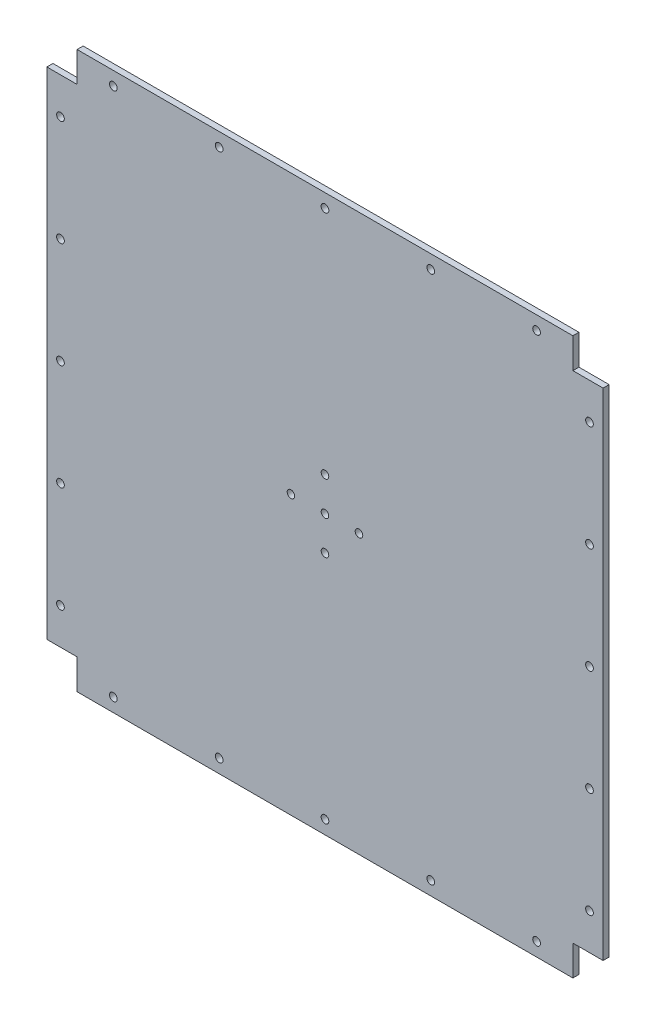
SolidWorks part; units mm, degrees
ref_plane "前视基准面" through (0, 0, 0) normal (0, 0, 1) x (1, 0, 0)
ref_plane "上视基准面" through (0, 0, 0) normal (0, 1, 0) x (1, 0, 0)
ref_plane "右视基准面" through (0, 0, 0) normal (1, 0, 0) x (0, 0, -1)
sketch "草图1" plane through (0, 0, 0) normal (0, 0, 1) x (1, 0, 0)
  line L1 (184, -184) -> (-184, -184)
  line L2 (184, -184) -> (184, 184)
  line L3 (184, 184) -> (-184, 184)
  line L4 (-184, -184) -> (-184, 184)
  line L5 (184, -184) -> (-184, 184) construction
  line L6 (184, 184) -> (-184, -184) construction
  point P0 (0, 0)
  dimension "D1" = 368
  dimension "D2" = 368
extrude "凸台-拉伸1" add sketch "草图1" along normal blind 4
sketch "草图3" plane through (0, 0, 4) normal (0, 0, 1) x (1, 0, 0)
  line L0 (0, -184) -> (0, -175) construction
  line L1 (-184, -184) -> (184, -184) construction
  circle A0 centre (0, -175) radius 2.55
  circle A1 centre (70, -175) radius 2.55
  circle A2 centre (140, -175) radius 2.55
  circle A3 centre (-70, -175) radius 2.55
  circle A4 centre (-140, -175) radius 2.55
  circle A30 centre (-175, 140) radius 2.55
  circle A31 centre (-175, 70) radius 2.55
  circle A32 centre (-175, -70) radius 2.55
  circle A33 centre (-175, -140) radius 2.55
  circle A34 centre (-175, 0) radius 2.55
  circle A35 centre (140, 175) radius 2.55
  circle A36 centre (70, 175) radius 2.55
  circle A37 centre (-70, 175) radius 2.55
  circle A38 centre (-140, 175) radius 2.55
  circle A39 centre (0, 175) radius 2.55
  circle A40 centre (175, -140) radius 2.55
  circle A41 centre (175, -70) radius 2.55
  circle A42 centre (175, 70) radius 2.55
  circle A43 centre (175, 140) radius 2.55
  circle A44 centre (175, 0) radius 2.55
  point P47 (10, -10)
  point P78 (0, 0)
  dimension "D1" = 5.1
  dimension "D2" = 9
  dimension "D3" = 3
  dimension "D4" = 3
  dimension "D6" = 4
extrude "切除-拉伸2" cut sketch "草图3" against normal through all
sketch "草图4" plane through (0, 0, 4) normal (0, 0, 1) x (1, 0, 0)
  line L0 (-164, 184) -> (-164, 164)
  line L1 (-184, -184) -> (-164, -184)
  line L2 (-184, -184) -> (-184, -164)
  line L3 (-184, -164) -> (-164, -164)
  line L4 (-164, -184) -> (-164, -164)
  line L5 (-184, 164) -> (-164, 164)
  line L6 (-184, 184) -> (-164, 184)
  line L7 (-184, 184) -> (-184, 164)
  line L8 (184, 164) -> (164, 164)
  line L9 (164, 184) -> (164, 164)
  line L10 (184, 184) -> (184, 164)
  line L11 (184, 184) -> (164, 184)
  line L12 (164, -184) -> (164, -164)
  line L13 (184, -164) -> (164, -164)
  line L14 (184, -184) -> (164, -184)
  line L15 (184, -184) -> (184, -164)
  point P20 (0, 0)
  dimension "D1" = 20
  dimension "D2" = 20
  dimension "D3" = 4
extrude "切除-拉伸3" cut sketch "草图4" against normal through all contours L0 L5 L7 L6 | L8 L9 L11 L10 | L12 L13 L15 L14 | L2 L1 L4 L3
sketch "草图5" plane through (0, 0, 4) normal (0, 0, 1) x (1, 0, 0)
  line L0 (-184, 0) -> (184, 0) construction
  line L1 (-184, 164) -> (-184, -164) construction
  line L2 (-184, 164) -> (-184, -164) construction
  line L3 (0, 184) -> (0, -184) construction
  line L4 (164, 184) -> (-164, 184) construction
  line L5 (-164, -184) -> (164, -184) construction
  line L6 (-10, 0) -> (-22.5, 0) construction
  line L11 (10, -10) -> (-10, 10) construction
  line L12 (10, 10) -> (-10, -10) construction
  line L13 (0, -10) -> (0, -22.5) construction
  line L14 (10, 0) -> (22.5, 0) construction
  line L15 (0, 10) -> (0, 22.5) construction
  line L16 (-173.9781, 173.9781) -> (0, 0) construction
  line L17 (-184, 0) -> (0, 184) construction
  line L19 (-14.489, 14.489) -> (-159.489, 14.489) construction
  line L20 (-14.489, 14.489) -> (-14.489, 159.489) construction
  line L21 (-14.489, 159.489) -> (-159.489, 159.489) construction
  line L22 (-159.489, 14.489) -> (-159.489, 159.489) construction
  line L23 (-14.489, 14.489) -> (-159.489, 159.489) construction
  line L24 (-14.489, 159.489) -> (-159.489, 14.489) construction
  circle A0 centre (0, 22.5) radius 2.5
  circle A1 centre (22.5, 0) radius 2.5
  circle A2 centre (-22.5, 0) radius 2.5
  circle A3 centre (0, -22.5) radius 2.5
  circle A4 centre (0, 0) radius 2.5
  point P4 (-86.989, 86.989)
  point P12 (0, 0)
  dimension "D7" = 5
  dimension "D8" = 5
  dimension "D9" = 5
  dimension "D10" = 5
  dimension "D11" = 5
  dimension "D1" = 20
  dimension "D2" = 20
  dimension "D3" = 12.5
  dimension "D4" = 12.5
  dimension "D5" = 12.5
  dimension "D6" = 12.5
  dimension "D12" = 145
  dimension "D13" = 145
extrude "切除-拉伸6" cut sketch "草图5" against normal blind 10
